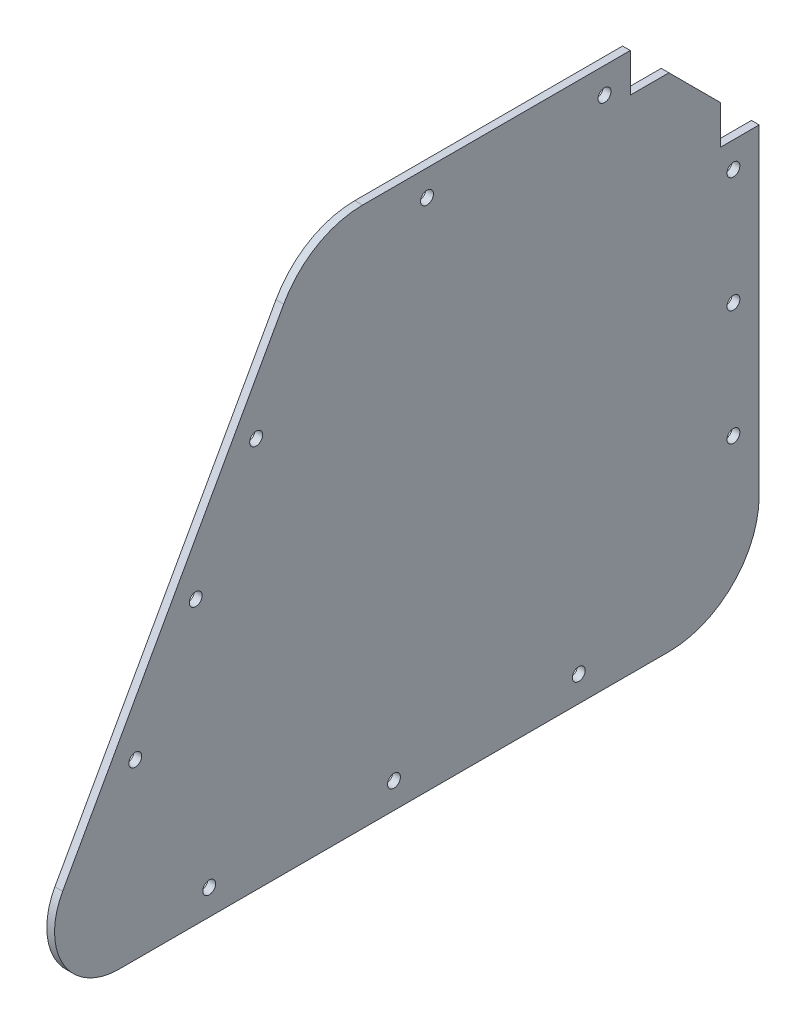
SolidWorks part; units mm, degrees
material "Acrylic (Medium-high impact)"
ref_plane "Front Plane" through (0, 0, 0) normal (0, 0, 1) x (1, 0, 0)
ref_plane "Top Plane" through (0, 0, 0) normal (0, 1, 0) x (1, 0, 0)
ref_plane "Right Plane" through (0, 0, 0) normal (1, 0, 0) x (0, 0, -1)
sketch "Sketch1" plane through (0, 0, 0) normal (1, 0, 0) x (0, 0, -1)
  line L0 (0, -1000) -> (0, 49000) construction
  line L1 (-1000, 0) -> (49000, 0) construction
  line L14 (-12.1885, 179.5) -> (106.6837, 179.5) construction
  line L15 (-29.6717, 169.2129) -> (-115.4252, 14.8564) construction
  line L16 (-106.6837, 0) -> (106.6837, 0) construction
  line L17 (126.6837, 20) -> (126.6837, 159.5) construction
  line L18 (-12.1885, 194.5) -> (106.6837, 194.5)
  line L19 (141.6837, 20) -> (141.6837, 159.5)
  line L20 (-106.6837, -15) -> (106.6837, -15)
  line L21 (-42.784, 176.4975) -> (-128.5376, 22.1411)
  arc A12 (-106.6837, 0) -> (-115.4252, 14.8564) centre (-106.6837, 10) cw construction
  arc A13 (106.6837, 0) -> (126.6837, 20) centre (106.6837, 20) ccw construction
  arc A14 (126.6837, 159.5) -> (106.6837, 179.5) centre (106.6837, 159.5) ccw construction
  arc A16 (-29.6717, 169.2129) -> (-12.1885, 179.5) centre (-12.1885, 159.5) cw construction
  arc A17 (141.6837, 159.5) -> (106.6837, 194.5) centre (106.6837, 159.5) ccw
  arc A18 (106.6837, -15) -> (141.6837, 20) centre (106.6837, 20) ccw
  arc A19 (-106.6837, -15) -> (-128.5376, 22.1411) centre (-106.6837, 10) cw
  arc A20 (-42.784, 176.4975) -> (-12.1885, 194.5) centre (-12.1885, 159.5) cw
  point P17 (47.2476, 179.5)
  point P18 (0, 0)
  dimension "D2" = 20
  dimension "D3" = 20
  dimension "D5" = 79.4361
  dimension "D1" = 10
  dimension "D4" = 20
  dimension "D6" = 213.3673
  dimension "D7" = 179.5
  dimension "D8" = 15
extrude "Boss-Extrude1" add sketch "Sketch1" along normal blind 3
sketch "Sketch2" plane through (3, 0, 0) normal (1, 0, 0) x (0, 0, -1)
  line L4 (-34.0424, 171.6411) -> (-119.796, 17.2846)
  line L5 (-34.0424, 171.6411) -> (-119.796, 17.2846) construction
  line L6 (-106.6837, -5) -> (106.6837, -5)
  line L7 (-106.6837, -5) -> (106.6837, -5) construction
  line L8 (131.6837, 20) -> (131.6837, 159.5)
  line L9 (131.6837, 20) -> (131.6837, 159.5) construction
  line L10 (106.6837, 184.5) -> (-12.1885, 184.5)
  line L11 (106.6837, 184.5) -> (-12.1885, 184.5) construction
  arc A4 (-12.1885, 184.5) -> (-34.0424, 171.6411) centre (-12.1885, 159.5) ccw
  arc A5 (-12.1885, 184.5) -> (-34.0424, 171.6411) centre (-12.1885, 159.5) ccw construction
  arc A6 (-119.796, 17.2846) -> (-106.6837, -5) centre (-106.6837, 10) ccw
  arc A7 (-119.796, 17.2846) -> (-106.6837, -5) centre (-106.6837, 10) ccw construction
  arc A8 (106.6837, -5) -> (131.6837, 20) centre (106.6837, 20) ccw
  arc A9 (106.6837, -5) -> (131.6837, 20) centre (106.6837, 20) ccw construction
  arc A10 (131.6837, 159.5) -> (106.6837, 184.5) centre (106.6837, 159.5) ccw
  arc A11 (131.6837, 159.5) -> (106.6837, 184.5) centre (106.6837, 159.5) ccw construction
  circle A32 centre (81.6837, 184.5) radius 2.5
  circle A33 centre (12.8115, 184.5) radius 2.5
  circle A34 centre (131.6837, 134.5) radius 2.5
  circle A35 centre (131.6837, 89.75) radius 2.5
  circle A44 centre (131.6837, 44.9999) radius 2.5
  circle A45 centre (71.6837, -5) radius 2.5
  circle A46 centre (0, -5) radius 2.5
  circle A47 centre (-71.6837, -5) radius 2.5
  circle A48 centre (-100.3703, 52.2509) radius 2.5
  circle A49 centre (-76.9192, 94.4629) radius 2.5
  circle A50 centre (-53.4682, 136.6748) radius 2.5
  point P1 (0, 0)
  point P3 (0, 0)
  point P4 (0, 0)
  point P7 (0, 0)
  point P8 (0, 0)
  point P11 (0, 0)
  point P13 (0, 0)
  point P15 (0, 0)
  point P19 (0, 0)
  point P23 (0, 0)
  point P25 (0, 0)
  dimension "D4" = 25
  dimension "D6" = 24.9999
  dimension "D7" = 35
  dimension "D8" = 35
  dimension "D9" = 40
  dimension "D10" = 40
  dimension "D2" = 5
  dimension "D5" = 25
  dimension "D3" = 25
  dimension "D1" = 10
extrude "Cut-Extrude1" cut sketch "Sketch2" against normal up to next
sketch "Sketch4" plane through (3, 0, 0) normal (1, 0, 0) x (0, 0, -1)
  line L0 (141.6837, 20) -> (141.6837, 159.5) construction
  line L1 (141.6837, 144.5) -> (126.6837, 144.5)
  line L2 (141.6837, 144.5) -> (141.6837, 194.5)
  line L3 (141.6837, 194.5) -> (91.6837, 194.5)
  line L4 (91.6837, 179.5) -> (91.6837, 194.5)
  line L5 (106.6837, 194.5) -> (-12.1885, 194.5) construction
  line L6 (126.6837, 144.5) -> (126.6837, 159.5)
  line L7 (91.6837, 179.5) -> (106.6837, 179.5)
  arc A0 (126.6837, 159.5) -> (106.6837, 179.5) centre (106.6837, 159.5) ccw
  dimension "D5" = 20
  dimension "D1" = 50
  dimension "D2" = 50
  dimension "D3" = 15
  dimension "D4" = 15
extrude "Cut-Extrude2" cut sketch "Sketch4" against normal up to next
sketch "Sketch5" plane through (3, 0, 0) normal (1, 0, 0) x (0, 0, -1)
  line L0 (106.6837, 179.5) -> (126.6837, 159.5)
  arc A0 (126.6837, 159.5) -> (106.6837, 179.5) centre (106.6837, 159.5) ccw construction
  arc A1 (126.6837, 159.5) -> (106.6837, 179.5) centre (106.6837, 159.5) ccw
extrude "Cut-Extrude3" cut sketch "Sketch5" against normal up to next
